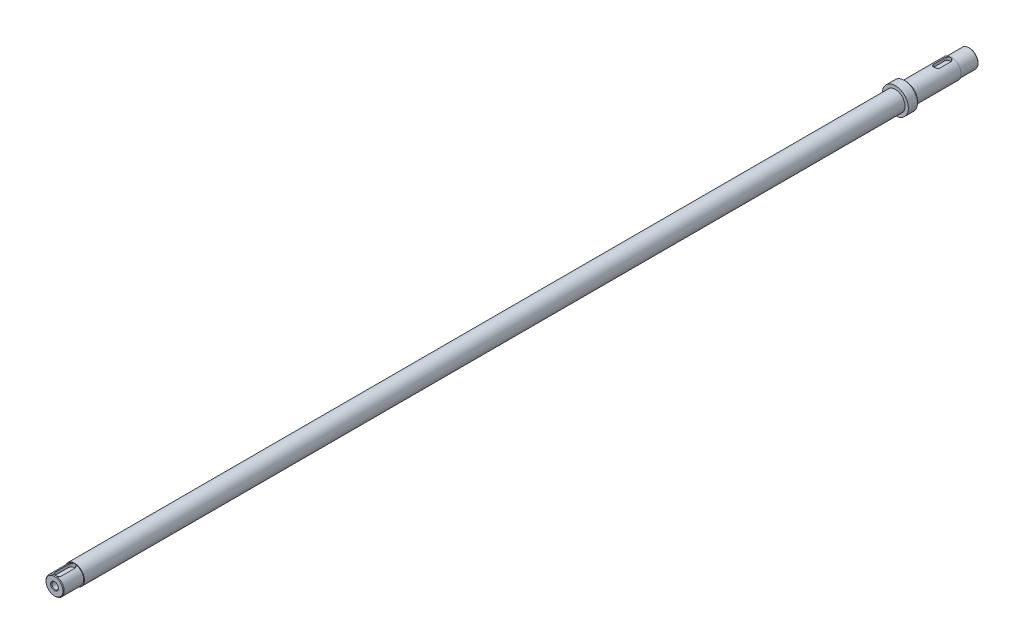
SolidWorks part; units mm, degrees
ref_plane "前视基准面" through (0, 0, 0) normal (0, 0, 1) x (1, 0, 0)
ref_plane "上视基准面" through (0, 0, 0) normal (0, 1, 0) x (1, 0, 0)
ref_plane "右视基准面" through (0, 0, 0) normal (1, 0, 0) x (0, 0, -1)
sketch "草图1" plane through (0, 0, 0) normal (0, 0, 1) x (1, 0, 0)
  circle A0 centre (0, 0) radius 7.5
  dimension "D2" = 15
extrude "拉伸1" add sketch "草图1" along normal blind 715
sketch "草图4" plane through (0, 0, 0) normal (0, 0, -1) x (-1, 0, 0)
  circle A0 centre (0, 0) radius 7.5
  circle A1 centre (0, 0) radius 7
extrude "切除-拉伸3" cut sketch "草图4" against normal blind 14
chamfer "倒角1" distance 0.5 angle 45 1 edges at (-7, 0, 0)
ref_plane "基准面1" through (0, 7, 0) normal (0, 1, 0) x (-1, 0, 0)
sketch "草图6" plane through (0, 0, 715) normal (0, 0, 1) x (1, 0, 0)
  circle A0 centre (0, 0) radius 7.5
  circle A1 centre (0, 0) radius 7
extrude "切除-拉伸5" cut sketch "草图6" against normal blind 27.5
chamfer "倒角2" distance 1 angle 45 1 edges at (7, 0, 715)
sketch "草图7" plane through (0, 0, 715) normal (0, 0, 1) x (1, 0, 0)
  circle A0 centre (0, 0) radius 7
  circle A1 centre (0, 0) radius 6.9
extrude "切除-拉伸6" cut sketch "草图7" against normal blind 12
ref_plane "基准面2" through (0, 0, 49) normal (0, 0, -1) x (-1, 0, 0)
sketch "草图8" plane through (0, 0, 49) normal (0, 0, -1) x (-1, 0, 0)
  circle A0 centre (0, 0) radius 7.5
  circle A1 centre (0, 0) radius 10
  dimension "D1" = 15
extrude "拉伸2" add sketch "草图8" against normal blind 8
chamfer "倒角3" distance 1 angle 45 1 edges at (0, 10, 49)
ref_plane "基准面3" through (0, 7, 0) normal (0, 1, 0) x (-1, 0, 0)
sketch "草图11" plane through (0, 7, 0) normal (0, 1, 0) x (-1, 0, 0)
  line L0 (7, 703) -> (-7, 703) construction
  line L1 (7.5, 687.5) -> (-7.5, 687.5) construction
  line L2 (-2.5, 700) -> (-2.5, 690)
  line L3 (2.5, 700) -> (2.5, 690)
  arc A0 (-2.5, 690) -> (2.5, 690) centre (0, 690) ccw
  arc A1 (2.5, 700) -> (-2.5, 700) centre (0, 700) ccw
  dimension "D1" = 3
  dimension "D2" = 5
  dimension "D3" = 5
  dimension "D4" = 2.5
extrude "切除-拉伸8" cut sketch "草图11" against normal blind 2.5
sketch "草图14" plane through (0, 7, 0) normal (0, 1, 0) x (-1, 0, 0)
  line L0 (-7, 14) -> (7, 14) construction
  line L1 (-2.5, 25) -> (-2.5, 17)
  line L2 (2.5, 25) -> (2.5, 17)
  arc A0 (-2.5, 17) -> (2.5, 17) centre (0, 17) ccw
  arc A1 (2.5, 25) -> (-2.5, 25) centre (0, 25) ccw
  dimension "D1" = 5
  dimension "D2" = 5
  dimension "D3" = 8
  dimension "D4" = 3
extrude "切除-拉伸11" cut sketch "草图14" against normal blind 2 and the other way blind 2.5
ref_plane "基准面4" through (0, 7, 0) normal (0, 1, 0) x (-1, 0, 0)
sketch "草图17" plane through (0, 0, 715) normal (0, 0, 1) x (1, 0, 0)
  circle A0 centre (0, 0) radius 6.9
extrude "切除-拉伸14" cut sketch "草图17" against normal blind 12
chamfer "倒角6" distance 0.5 angle 45 1 edges at (7, 0, 703)
sketch "草图20" plane through (0, 0, 703) normal (0, 0, 1) x (1, 0, 0)
  circle A0 centre (0, 0) radius 2.5
  dimension "D1" = 5
extrude "切除-拉伸16" cut sketch "草图20" against normal blind 15
chamfer "倒角7" distance 0.5 angle 45 1 edges at (2.5, 0, 703)
